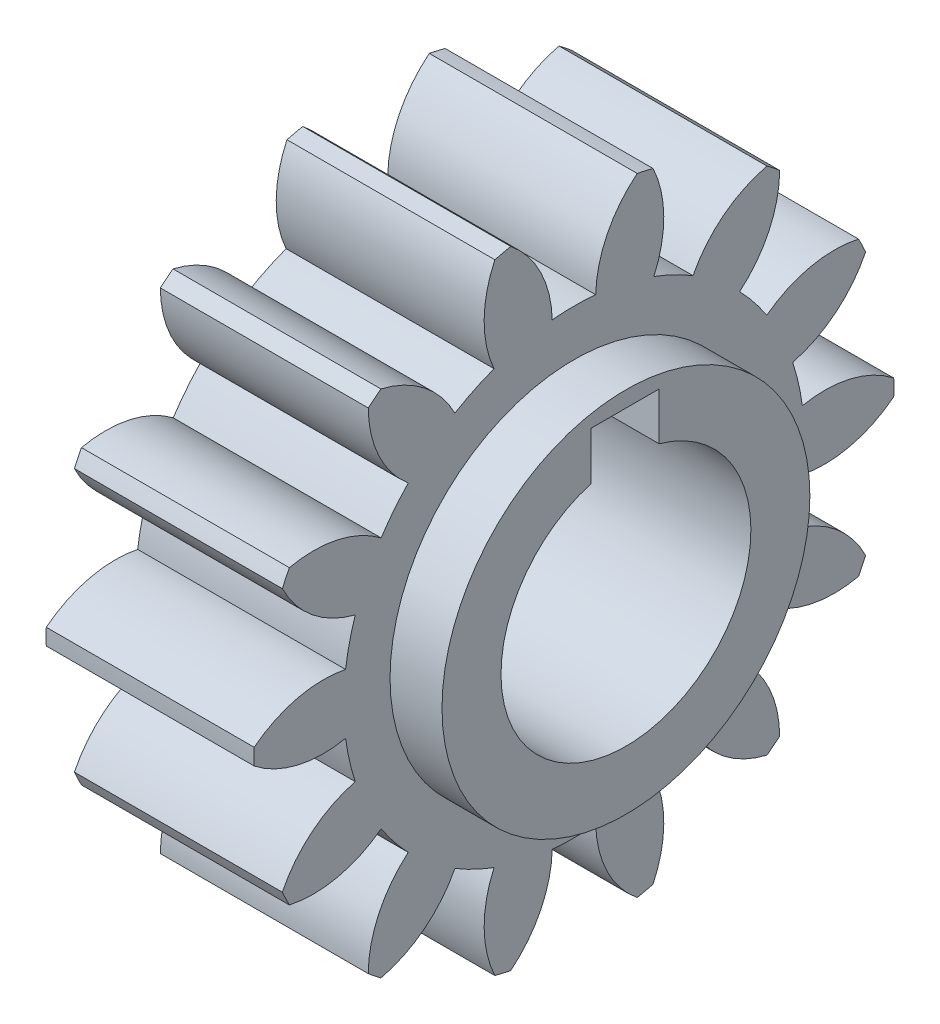
SolidWorks part; units mm, degrees
ref_plane "Plane1" through (0, 0, 0) normal (0, 0, 1) x (1, 0, 0)
ref_plane "Plane2" through (0, 0, 0) normal (0, 1, 0) x (1, 0, 0)
ref_plane "Plane3" through (0, 0, 0) normal (1, 0, 0) x (0, 0, -1)
sketch "HoldingSke" plane through (0, 0, 0) normal (0, 1, 0) x (1, 0, 0)
  line L0 (0, 0) -> (492.9102, -122.8963)
  line L1 (-15, 0) -> (100, 0) construction
  line L2 (0, 0) -> (-2.1039, 2.3779)
  line L3 (0, 0) -> (-11.863, 4.5341)
  line L4 (0, 0) -> (8.3795, 2.0892)
  line L5 (0, 0) -> (-47.5972, -17.7524)
  line L6 (0, 0) -> (-5.4745, -3.6936)
  line L7 (-2.1039, 2.3779) -> (8.8308, 51.9871)
  line L8 (-76.2, 54.61) -> (-67.9958, 54.61)
  line L9 (-71.009, 38.7566) -> (-53.1078, 45.2721)
  line L10 (-76.2, 71.12) -> (104.1128, 71.12)
  line L11 (0, 0) -> (-6.604, 0)
  line L12 (-76.2, 101.6) -> (-76.1492, 101.6)
  line L13 (24.9733, 27.94) -> (52.9518, 28.4284)
  line L14 (24.9733, 27.94) -> (25.0241, 27.9398)
  line L15 (24.9733, 27.94) -> (100.4021, 29.52)
  circle A0 centre (0, 0) radius 3.9688
  circle A1 centre (0, 0) radius 7.3152
  circle A2 centre (0, 0) radius 38.1
  circle A3 centre (0, 0) radius 3.9688
  dimension "Num_teeth" = 14
  dimension "H" = 19.05
  dimension "Pitch_radius" = 180.3128
  dimension "Width" = 6.604
  dimension "Thickness" = 6.604
sketch "BasProSke" plane through (0, 0, 0) normal (0, 1, 0) x (1, 0, 0)
  line L0 (-10, 0) -> (60, 0) construction
  line L1 (0, 0) -> (0, 10.16)
  line L2 (0, 0) -> (6.604, 0)
  line L3 (6.604, 0) -> (6.604, 10.16)
  line L4 (6.604, 10.16) -> (0, 10.16)
  dimension "Thickness" = 6.604
  dimension "Diameter" = 20.32
revolve "Base-Revolve" add sketch "BasProSke" angle 360 about L0
sketch "TooCutSke" plane through (0, 0, 0) normal (1, 0, 0) x (0, 0, -1)
  line L1 (0, 0) -> (0, 107) construction
  line L2 (0, 0) -> (-1.0842, 8.8236) construction
  line L3 (0, 0) -> (-3.9358, 17.2439) construction
  line L4 (-1.0842, 8.8236) -> (-1.9679, 8.6219) construction
  arc A0 (0.6903, 7.2826) -> (-0.6903, 7.2826) centre (0, 0) ccw
  arc A1 (2.0345, 9.9801) -> (-2.0345, 9.9801) centre (0, 0) ccw
  circle A2 centre (0, 0) radius 8.89 construction
  circle A3 centre (0, 0) radius 8.3539 construction
  arc A4 (-0.6903, 7.2826) -> (-2.0345, 9.9801) centre (-4.2452, 7.1948) ccw
  arc A5 (2.0345, 9.9801) -> (0.6903, 7.2826) centre (4.2452, 7.1948) ccw
extrude "ToothCut" cut sketch "TooCutSke" along normal through all
fillet "Breaks" [suppressed] radius 0.0254 tangent propagation no
fillet "RootFillets" [suppressed] radius 0.3048
pattern_circular "TeethCuts" count 14 every 25.714 about axis through (-10, 0, 0) along (1, 0, 0) of "ToothCut", "RootFillets", "Breaks"
sketch "HubNeaOneSke" plane through (0, 0, 0) normal (-1, 0, 0) x (0, 0, 1)
  circle A0 centre (0, 0) radius 7.3152
  dimension "Diameter" = 14.6304
extrude "HubNearOne" [suppressed] add sketch "HubNeaOneSke" along normal blind 44.1961
sketch "HubNeaBotSke" plane through (0, 0, 0) normal (-1, 0, 0) x (0, 0, 1)
  circle A0 centre (0, 0) radius 7.3152
  dimension "Diameter" = 14.6304
extrude "HubNearBoth" [suppressed] add sketch "HubNeaBotSke" along normal blind 22.098
ref_plane "FarPln" through (6.604, 0, 0) normal (1, 0, 0) x (0, 0, -1)
sketch "HubFarSke" plane through (6.604, 0, 0) normal (1, 0, 0) x (0, 0, -1)
  circle A0 centre (0, 0) radius 7.3152
  dimension "Diameter" = 14.6304
extrude "HubFar" [suppressed] add sketch "HubFarSke" along normal blind 22.098
sketch "BorSke" plane through (0, 0, 0) normal (1, 0, 0) x (0, 0, -1)
  circle A0 centre (0, 0) radius 3.9688
  dimension "Diameter" = 7.9375
extrude "Bore" cut sketch "BorSke" along normal mid plane 101.6001
sketch "KeySke" plane through (0, 0, 0) normal (1, 0, 0) x (0, 0, -1)
  line L0 (-0.127, 0) -> (-0.127, 4.2355)
  line L1 (-0.127, 4.2355) -> (0.127, 4.2355)
  line L2 (0.127, 4.2355) -> (0.127, 0)
  line L3 (0, 0) -> (0, 34) construction
  line L4 (-0.127, 0) -> (0.127, 0)
  dimension "Width" = 0.254
extrude "Keyway" [suppressed] cut sketch "KeySke" along normal mid plane 101.6001
pattern_circular "Keyway2" [suppressed] count 2 every 90 about axis through (-10, 0, 0) along (1, 0, 0) reverse direction yes
sketch "Sketch1" plane through (6.604, 0, 0) normal (1, 0, 0) x (0, 0, -1)
  circle A0 centre (0, 0) radius 3.9688
  circle A1 centre (0, 0) radius 5.842
extrude "Boss-Extrude1" add sketch "Sketch1" along normal blind 1.651
sketch "Sketch2" plane through (0, 0, 0) normal (-1, 0, 0) x (0, 0, 1)
  line L0 (-1.0531, 0) -> (1.1059, 0)
  line L1 (1.1059, 0) -> (1.1059, 5.334)
  line L2 (1.1059, 5.334) -> (-1.0531, 5.334)
  line L3 (-1.0531, 5.334) -> (-1.0531, 0)
  dimension "D1" = 2.159
  dimension "D2" = 5.334
extrude "Cut-Extrude1" cut sketch "Sketch2" against normal through all
equation "' \"Pitch@HoldingSke\" = 4"
equation "' \"Num_teeth@HoldingSke\" = 12"
equation "' \"Ap@HoldingSke\" =  20"
equation "' \"Ap@HoldingSke\" = 20"
equation "' \"Width@HoldingSke\" = 0.5"
equation "' \"Hub_dia@HoldingSke\"= 1"
equation "' \"Hub_dia@HoldingSke\" = 1"
equation "' \"Overall_len@HoldingSke\" = 1.0"
equation "' \"Bore@HoldingSke\" = 0.75"
equation "' \"T_dim@HoldingSke\" = 0.85"
equation "' \"Width@KeySke\" = 0.25"
equation "' \"Show_teeth@HoldingSke\" = 13"
equation "' \"Backlash@HoldingSke\" = 0.009"
equation "' \"Addendum_fac@HoldingSke\" = 1.0"
equation "' \"Dedendum_fac@HoldingSke\" = 1.25"
equation "' \"Dedendum_add@HoldingSke\" = 0.00005"
equation "' \"Clearance_fac@HoldingSke\" = 0.25"
equation "' \"Pitch@HoldingSke\" = 0.5"
equation "' \"Num_teeth@HoldingSke\" = 23"
equation "' \"Show_teeth@HoldingSke\" = 23"
equation "' \"Backlash@HoldingSke\" = 0.0375"
equation "\"Overcut_dia@TooCutSke\" = (\"Num_teeth@HoldingSke\" + 2 * \"Addendum_fac@HoldingSke\") / \"Pitch@HoldingSke\" + 0.002"
equation "\"Pitch_dia@TooCutSke\" = \"Num_teeth@HoldingSke\" / \"Pitch@HoldingSke\""
equation "\"Base_dia@TooCutSke\" = \"Num_teeth@HoldingSke\" / \"Pitch@HoldingSke\" * cos((\"Ap@HoldingSke\"  * 3.14159265 / 180))"
equation "\"Root_dia@TooCutSke\" = (\"Num_teeth@HoldingSke\" + 2) / \"Pitch@HoldingSke\" - 2 * (\"Addendum_fac@HoldingSke\" + \"Dedendum_fac@HoldingSke\") / \"Pitch@HoldingSke\" - \"Dedendum_add@HoldingSke\" * 2"
equation "\"Half_ang@TooCutSke\" = 180 / \"Num_teeth@HoldingSke\""
equation "\"Half_CT@TooCutSke\" = \"Num_teeth@HoldingSke\" / \"Pitch@HoldingSke\" * sin((3.14159265 / 2 / \"Num_teeth@HoldingSke\")) / 2 - 7 * \"Backlash@HoldingSke\" / 4"
equation "\"Flank_rad@TooCutSke\" = \"Num_teeth@HoldingSke\" / \"Pitch@HoldingSke\" / 5"
equation "\"Radius@RootFillets\" = \"Clearance_fac@HoldingSke\" / \"Pitch@HoldingSke\" + \"Dedendum_add@HoldingSke\""
equation "\"Break_rad@Breaks\" = 0.02 / \"Pitch@HoldingSke\""
equation "\"Thickness@HoldingSke\" = \"Width@HoldingSke\""
equation "\"OAL@HoldingSke\" = \"Thickness@HoldingSke\""
equation "\"MHD@HoldingSke\" = (\"Num_teeth@HoldingSke\" + 2) / \"Pitch@HoldingSke\" - 2 * (\"Addendum_fac@HoldingSke\" + \"Dedendum_fac@HoldingSke\")  / \"Pitch@HoldingSke\" - \"Dedendum_add@HoldingSke\" * 2"
equation "\"MBD@HoldingSke\" = (\"Num_teeth@HoldingSke\" + 2) / \"Pitch@HoldingSke\" - 2 * (\"Addendum_fac@HoldingSke\" + \"Dedendum_fac@HoldingSke\")  / \"Pitch@HoldingSke\" - \"Dedendum_add@HoldingSke\" * 2 - 0.002"
equation "\"MHD@HoldingSke\" = ((sgn( \"MHD@HoldingSke\" - \"Hub_dia@HoldingSke\" )-1)*( \"MHD@HoldingSke\" - \"Hub_dia@HoldingSke\" ))/-2+ \"Hub_dia@HoldingSke\""
equation "\"MBD@HoldingSke\" = ((sgn( \"MBD@HoldingSke\" - \"Bore@HoldingSke\" )-1)*( \"MBD@HoldingSke\" - \"Bore@HoldingSke\" ))/-2+ \"Bore@HoldingSke\""
equation "\"OAL@HoldingSke\" = ((sgn( \"OAL@HoldingSke\" - \"Overall_len@HoldingSke\" )+1)*( \"OAL@HoldingSke\" - \"Overall_len@HoldingSke\" ))/2 + \"Overall_len@HoldingSke\" + 0.000002"
equation "\"Num_teeth@TeethCuts\" = int( \"Show_teeth@HoldingSke\" ) + 1"
equation "\"Num_teeth@TeethCuts\" = ((sgn( \"Num_teeth@TeethCuts\" - \"Num_teeth@HoldingSke\" )-1)*( \"Num_teeth@TeethCuts\" - \"Num_teeth@HoldingSke\" ))/-2+ \"Num_teeth@HoldingSke\""
equation "\"Num_teeth@TeethCuts\" = ((sgn( \"Num_teeth@TeethCuts\" - 2.0)+1)*( \"Num_teeth@TeethCuts\" - 2.0))/2 +2.0"
equation "\"Angle@TeethCuts\" = 360.0 / \"Num_teeth@HoldingSke\""
equation "\"Diameter@BasProSke\" = (\"Num_teeth@HoldingSke\" + 2 * \"Addendum_fac@HoldingSke\") / \"Pitch@HoldingSke\""
equation "\"Thickness@BasProSke\"  = \"Thickness@HoldingSke\""
equation "' \"Fillet_rad@BasProSke\" =  \"Thickness@HoldingSke\" * 0.05"
equation "' \"Fillet_rad@BasProSke\" = \"Thickness@HoldingSke\" * 0.05"
equation "\"MHD@HoldingSke\" = ((sgn( \"MHD@HoldingSke\" - \"Root_dia@TooCutSke\" )-1)*( \"MHD@HoldingSke\" - \"Root_dia@TooCutSke\" ))/-2+ \"Root_dia@TooCutSke\""
equation "\"Diameter@HubNeaOneSke\" = \"MHD@HoldingSke\""
equation "\"Length@HubNearOne\" = \"OAL@HoldingSke\" - \"Thickness@BasProSke\""
equation "\"Diameter@HubNeaBotSke\" = \"MHD@HoldingSke\""
equation "\"Length@HubNearBoth\" = ( \"OAL@HoldingSke\" - \"Thickness@BasProSke\" ) / 2.0"
equation "\"Thickness@FarPln\" = \"Thickness@BasProSke\""
equation "\"Diameter@HubFarSke\" = \"MHD@HoldingSke\""
equation "\"Length@HubFar\" = ( \"OAL@HoldingSke\" - \"Thickness@BasProSke\" ) / 2.0"
equation "\"Diameter@BorSke\" = \"MBD@HoldingSke\""
equation "\"D1@Bore\" = \"OAL@HoldingSke\" * 2.0"
equation "\"D1@Keyway\" = \"OAL@HoldingSke\" * 2.0"
equation "\"Offset@KeySke\" = \"T_dim@HoldingSke\" - \"MBD@HoldingSke\" / 2.0"
